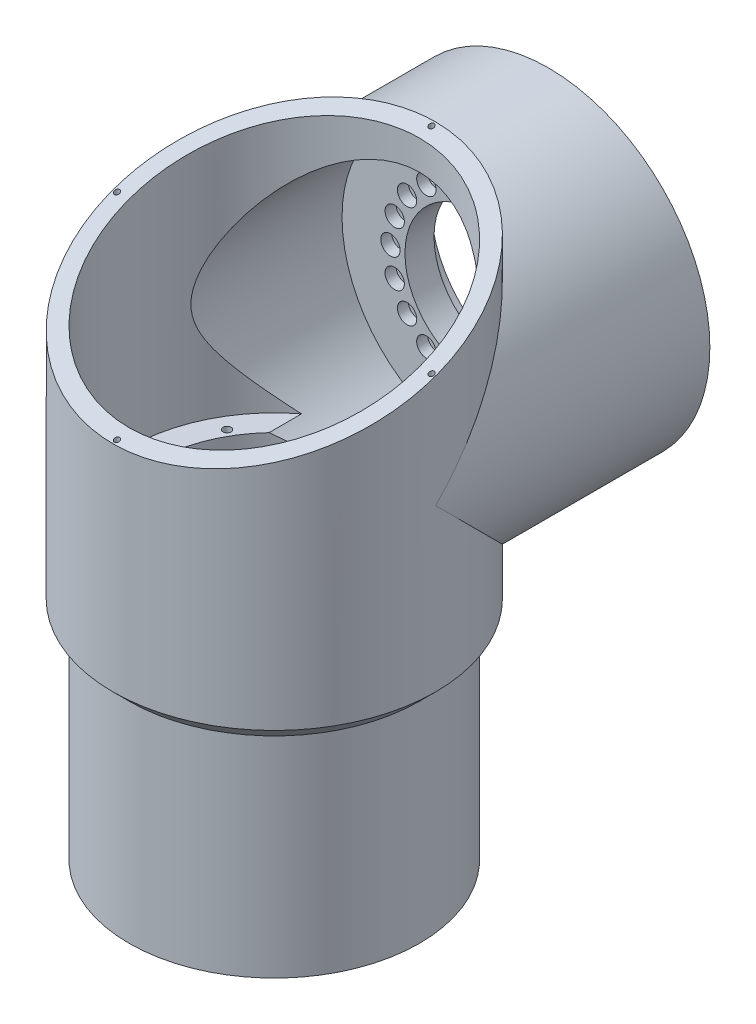
SolidWorks part; units mm, degrees
ref_plane "前视基准面" through (0, 0, 0) normal (0, 0, 1) x (1, 0, 0)
ref_plane "上视基准面" through (0, 0, 0) normal (0, 1, 0) x (1, 0, 0)
ref_plane "右视基准面" through (0, 0, 0) normal (1, 0, 0) x (0, 0, -1)
sketch "草图1" plane through (0, 0, 0) normal (0, 0, 1) x (1, 0, 0)
  circle A0 centre (0, 0) radius 50
  dimension "D1" = 100
extrude "凸台-拉伸1" add sketch "草图1" along normal blind 85
sketch "草图2" plane through (0, 0, 0) normal (0, 1, 0) x (1, 0, 0)
  line L0 (-50, -85) -> (50, -85) construction
  circle A0 centre (0, -85) radius 50
extrude "凸台-拉伸2" add sketch "草图2" along normal blind 53 and the other way blind 120
sketch "草图3" plane through (0, 0, 0) normal (0, 0, -1) x (-1, 0, 0)
  circle A0 centre (0, 0) radius 42
  dimension "D1" = 84
extrude "切除-拉伸1" cut sketch "草图3" against normal blind 4.5
sketch "草图4" plane through (0, 0, 4.5) normal (0, 0, -1) x (-1, 0, 0)
  circle A0 centre (0, 0) radius 32
  dimension "D1" = 64
extrude "切除-拉伸2" cut sketch "草图4" against normal blind 8.5
sketch "草图5" plane through (0, -120, 0) normal (0, -1, 0) x (1, 0, 0)
  circle A0 centre (0, 85) radius 37
  dimension "D1" = 74
extrude "切除-拉伸3" cut sketch "草图5" against normal blind 20.5
sketch "草图6" plane through (0, -120, 0) normal (0, -1, 0) x (1, 0, 0)
  circle A0 centre (0, 85) radius 45
  dimension "D1" = 90
extrude "切除-拉伸4" cut sketch "草图6" against normal blind 65 flip side to cut contours A0
chamfer "倒角1" distance 5 angle 45 1 edges at (0, -55, 35)
hole_wizard "M3 螺纹孔1" positions "草图8" profile "草图7" tap size "M3" standard "GB"
sketch "草图8" plane through (0, -99.5, 0) normal (0, -1, 0) x (-1, 0, 0)
  line L0 (0, -85) -> (0, -117.9255) construction
  circle A0 centre (0, -85) radius 32 construction
  point P0 (0, -117)
  dimension "D1" = 64
sketch "草图7" plane through (0, -99.5, 117) normal (1, 0, 0) x (0, 0, -1)
  line L0 (0, 0) -> (0, 8.2511)
  line L1 (0, 8.2511) -> (1.25, 7.5)
  line L2 (1.25, 7.5) -> (1.25, 0)
  line L5 (1.25, 0) -> (0, 0)
  line L10 (0, 8.2511) -> (-1.25, 7.5) construction
  line L11 (0, -6.35) -> (0, 107.95) construction
  dimension "螺纹孔钻头直径" = 2.5
  dimension "螺纹孔钻头深度" = 7.5
  dimension "导头角度" = 118
cosmetic thread "孔螺蚊线1" parameters "D1"=6, "D2"=3
ref_axis "基准轴1" through (0, -50, 85) along (0, 1, 0)
pattern_circular "阵列(圆周)1" count 12 over 360 about axis through (0, -50, 85) along (0, 1, 0) of "M3 螺纹孔1"
sketch "草图9" plane through (0, -99.5, 0) normal (0, -1, 0) x (1, 0, 0)
  circle A0 centre (0, 85) radius 20
  dimension "D1" = 40
extrude "切除-拉伸5" cut sketch "草图9" against normal through all
sketch "草图10" plane through (0, 53, 0) normal (0, 1, 0) x (1, 0, 0)
  circle A0 centre (0, -85) radius 37.5
  dimension "D1" = 75
extrude "切除-拉伸6" cut sketch "草图10" against normal offset from surface (142.5 mm away) 10 up to face at (0, -99.5, 65)
sketch "草图11" plane through (0, 53, 0) normal (0, 1, 0) x (1, 0, 0)
  circle A0 centre (0, -85) radius 45
  dimension "D1" = 90
extrude "切除-拉伸7" cut sketch "草图11" against normal offset from surface (84.9 mm away) 57.6 up to face at (0, -89.5, 47.5)
sketch "草图15" plane through (0, 0, 13) normal (0, 0, -1) x (-1, 0, 0)
  circle A0 centre (0, 0) radius 22.5
  dimension "D1" = 45
extrude "切除-拉伸8" cut sketch "草图15" against normal blind 20 contours A0
ref_plane "基准面1" through (0, 0, 22) normal (0, 0, 1) x (1, 0, 0)
sketch "草图17" plane through (0, 0, 22) normal (0, 0, 1) x (1, 0, 0)
  circle A0 centre (0, 0) radius 42
extrude "切除-拉伸9" cut sketch "草图17" along normal blind 50
hole_wizard "打孔尺寸(%根据)内六角圆柱头螺钉的类型1" positions "草图21" profile "草图20" counterbore size "M3" standard "GB" end condition through all
sketch "草图21" plane through (0, 0, 22) normal (0, 0, 1) x (1, 0, 0)
  line L0 (0, 0) -> (-49.0939, 0) construction
  circle A0 centre (0, 0) radius 27 construction
  point P0 (-27, 0)
  dimension "D1" = 54
sketch "草图20" plane through (-27, 0, 22) normal (1, 0, 0) x (0, -1, 0)
  line L0 (0, 0) -> (0, 22)
  line L1 (0, 22) -> (1.8, 22)
  line L3 (1.8, 22) -> (1.8, 3.4)
  line L4 (1.8, 3.4) -> (3, 3.4)
  line L5 (3, 3.4) -> (3, 0)
  line L7 (3, 0) -> (0, 0)
  line L11 (0, -6.35) -> (0, 107.95) construction
  dimension "通孔孔直径" = 3.6
  dimension "通孔孔深度" = 22
  dimension "柱形沉头孔直径" = 6
  dimension "柱形沉头孔深度" = 3.4
ref_axis "基准轴2" through (0, 0, 85) along (0, 0, -1)
pattern_circular "阵列(圆周)3" count 20 over 360 about axis through (0, 0, 85) along (0, 0, -1) of "打孔尺寸(%根据)内六角圆柱头螺钉的类型1"
sketch "草图22" plane through (0, 0, 0) normal (1, 0, 0) x (0, 0, -1)
  line L0 (-35, 53) -> (-135, 53)
  line L1 (-135, 53) -> (-135, 16.603)
  line L2 (-135, 53) -> (-135, -50) construction
  line L3 (-135, 16.603) -> (-35, 53)
  dimension "D1" = 20
extrude "切除-拉伸10" cut sketch "草图22" against normal through all and the other way through all
hole_wizard "M3 螺纹孔3" positions "草图24" profile "草图23" tap size "M3" standard "GB"
sketch "草图24" plane through (0, -31.9, 0) normal (0, 1, 0) x (1, 0, 0)
  line L0 (0, -85) -> (0, -142.6179) construction
  circle A0 centre (0, -85) radius 40 construction
  point P0 (0, -125)
  dimension "D1" = 80
sketch "草图23" plane through (0, -31.9, 125) normal (1, 0, 0) x (0, 0, 1)
  line L0 (0, 0) -> (0, 8.2511)
  line L1 (0, 8.2511) -> (1.25, 7.5)
  line L2 (1.25, 7.5) -> (1.25, 0)
  line L5 (1.25, 0) -> (0, 0)
  line L10 (0, 8.2511) -> (-1.25, 7.5) construction
  line L11 (0, -6.35) -> (0, 107.95) construction
  dimension "螺纹孔钻头直径" = 2.5
  dimension "螺纹孔钻头深度" = 7.5
  dimension "导头角度" = 118
cosmetic thread "孔螺蚊线3" parameters "D1"=6, "D2"=3
pattern_circular "阵列(圆周)4" count 5 every 30 about axis through (0, -50, 85) along (0, 1, 0) of "M3 螺纹孔3"
mirror "镜向1" about plane through (0, 0, 0) normal (1, 0, 0) of "阵列(圆周)4"
ref_plane "基准面2" through (0, 53, 0) normal (0, 1, 0) x (1, 0, 0)
sketch "草图25" plane through (0, 53, 0) normal (0, 1, 0) x (1, 0, 0)
  line L0 (0, -85) -> (0, -148.4209) construction
  circle A0 centre (0, -85) radius 48.75 construction
  circle A1 centre (0, -133.75) radius 0.8
  dimension "D1" = 97.5
  dimension "D2" = 1.6
extrude "切除-拉伸11" cut sketch "草图25" against normal blind 47
sketch "草图26" plane through (0, 53, 0) normal (0, 1, 0) x (1, 0, 0)
  line L0 (-63.4674, -85) -> (58.0971, -85) construction
  circle A0 centre (0, -85) radius 48.75 construction
  circle A1 centre (-48.75, -85) radius 0.8
  circle A2 centre (48.75, -85) radius 0.8
  dimension "D1" = 97.5
  dimension "D2" = 1.6
  dimension "D3" = 1.6
extrude "切除-拉伸12" cut sketch "草图26" against normal blind 25
sketch "草图27" plane through (0, 53, 0) normal (0, 1, 0) x (1, 0, 0)
  line L0 (0, -85) -> (0, -6.5957) construction
  circle A0 centre (0, -85) radius 48.75 construction
  circle A1 centre (0, -36.25) radius 0.8
  dimension "D1" = 97.5
  dimension "D2" = 1.6
extrude "切除-拉伸13" cut sketch "草图27" against normal blind 5
